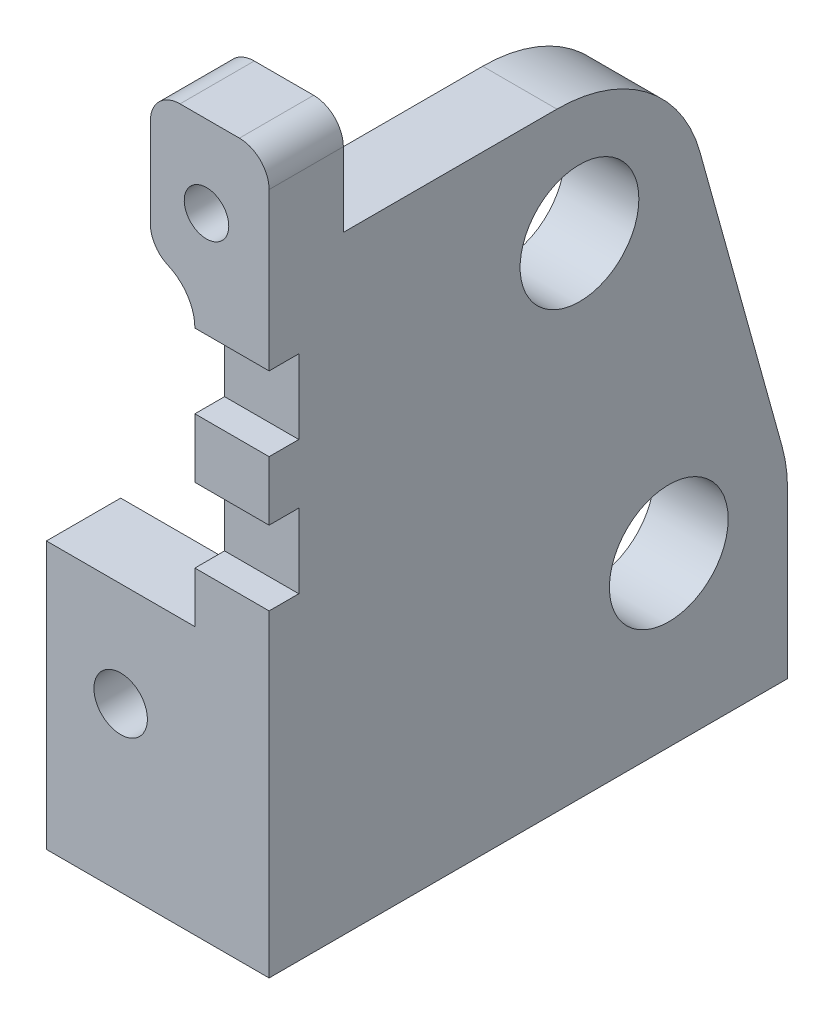
SolidWorks part; units mm, degrees
ref_plane "前视基准面" through (0, 0, 0) normal (0, 0, 1) x (1, 0, 0)
ref_plane "上视基准面" through (0, 0, 0) normal (0, 1, 0) x (1, 0, 0)
ref_plane "右视基准面" through (0, 0, 0) normal (1, 0, 0) x (0, 0, -1)
sketch "草图1" plane through (0, 0, 0) normal (1, 0, 0) x (0, 0, -1)
  line L1 (-20.9094, -33) -> (14.0173, -33)
  line L3 (-20.9094, 8) -> (-20.9094, -33)
  line L4 (-20.9094, 8) -> (6.082, 8)
  line L5 (6.082, 8) -> (14.0173, -20.5908)
  line L6 (14.0173, -20.5908) -> (14.0173, -33)
  line L7 (0, 0) -> (6.0173, -21.6804) construction
  circle A0 centre (0, 0) radius 4
  circle A1 centre (6.0173, -21.6804) radius 4
  point P13 (14.0173, -26.7954)
  dimension "D1" = 20.9094
  dimension "D5" = 8
  dimension "D7" = 8
  dimension "D2" = 33
  dimension "D3" = 22.5
  dimension "D4" = 21.6804
  dimension "D6" = 8
  dimension "D8" = 8
extrude "凸台-拉伸1" add sketch "草图1" along normal blind 5
sketch "草图2" plane through (0, 0, 0) normal (-1, 0, 0) x (0, 0, 1)
  line L0 (20.9094, -15) -> (20.9094, -33)
  line L1 (20.9094, 8) -> (20.9094, -33) construction
  line L3 (20.9094, -33) -> (7.9094, -33)
  line L4 (20.9094, -33) -> (-14.0173, -33) construction
  line L5 (7.9094, -33) -> (7.9094, -28)
  line L6 (7.9094, -28) -> (15.9094, -28)
  line L7 (15.9094, -28) -> (15.9094, -15)
  line L8 (15.9094, -15) -> (20.9094, -15)
  dimension "D1" = 5
  dimension "D2" = 5
  dimension "D3" = 13
  dimension "D4" = 8
extrude "凸台-拉伸2" add sketch "草图2" along normal blind 10
fillet "圆角1" radius 10 2 edges at (2.5, -20.5908, -14.0173) (2.5, 8, -6.082)
sketch "草图7" plane through (0, 8, 0) normal (0, 1, 0) x (1, 0, 0)
  line L1 (5, -20.9094) -> (-3, -20.9094)
  line L2 (5, -20.9094) -> (5, -15.9094)
  line L3 (5, -15.9094) -> (-3, -15.9094)
  line L4 (-3, -20.9094) -> (-3, -15.9094)
  dimension "D1" = 5
  dimension "D2" = 8
extrude "凸台-拉伸3" add sketch "草图7" along normal blind 7 and the other way blind 3
hole_wizard "打孔尺寸(%根据十字)槽半沉头木螺钉的类型1" positions "草图3" profile "草图4" countersink size "M3" standard "GB" end condition through all
sketch "草图3" plane through (0, 0, 15.9094) normal (0, 0, -1) x (-1, 0, 0)
  line L0 (10, -15) -> (10, -28) construction
  line L1 (10, -28) -> (0, -28) construction
  point P0 (5, -22)
  point P11 (0, 0)
  point P12 (0, 0)
  point P13 (0, 0)
  dimension "D1" = 5
  dimension "D2" = 6
sketch "草图4" plane through (-5, -22, 15.9094) normal (1, 0, 0) x (0, 1, 0)
  line L0 (0, 0) -> (0, 5)
  line L1 (0, 5) -> (1.8, 5)
  line L2 (1.8, 5) -> (1.8, 1.5)
  line L3 (1.8, 1.5) -> (3.3, 0)
  line L5 (3.3, 0) -> (0, 0)
  line L6 (-1.8, 1.5) -> (-3.3, 0) construction
  line L11 (0, -6.35) -> (0, 107.95) construction
  dimension "通孔孔直径" = 3.6
  dimension "通孔孔深度" = 5
  dimension "近端锥形沉头孔直径" = 6.6
  dimension "近端锥形沉头孔角度" = 90
hole_wizard "打孔尺寸(%根据十字)槽半沉头木螺钉的类型2" positions "草图5" profile "草图6" countersink size "M3" standard "GB" end condition through all
sketch "草图5" plane through (0, -28, 0) normal (0, 1, 0) x (1, 0, 0)
  line L0 (-10, -7.9094) -> (0, -7.9094) construction
  line L2 (0, -1.5205) -> (0, -15.9094) construction
  point P0 (-5, -11.9094)
  dimension "D1" = 4
  dimension "D2" = 5
sketch "草图6" plane through (-5, -28, 11.9094) normal (1, 0, 0) x (0, 0, 1)
  line L0 (0, 0) -> (0, 5)
  line L1 (0, 5) -> (1.8, 5)
  line L2 (1.8, 5) -> (1.8, 1.5)
  line L3 (1.8, 1.5) -> (3.3, 0)
  line L5 (3.3, 0) -> (0, 0)
  line L6 (-1.8, 1.5) -> (-3.3, 0) construction
  line L11 (0, -6.35) -> (0, 107.95) construction
  dimension "通孔孔直径" = 3.6
  dimension "通孔孔深度" = 5
  dimension "近端锥形沉头孔直径" = 6.6
  dimension "近端锥形沉头孔角度" = 90
fillet "圆角2" radius 2 3 edges at (-3, 5, 18.4094) (-3, 15, 18.4094) (5, 15, 18.4094)
fillet "圆角3" radius 3 1 edges at (0, 5, 18.4094)
hole_wizard "大小mm Transitional 暗销孔1" positions "草图8" profile "草图9" hole size "Ø3.0" standard "GB" end condition through all
sketch "草图8" plane through (0, 0, 15.9094) normal (0, 0, -1) x (-1, 0, 0)
  line L0 (-16.2809, 0) -> (3.92, 0) construction
  point P0 (-0.7825, 9.5089)
  point P8 (0, 0)
  point P13 (-7.9564, 0)
  dimension "D1" = 0.7825
  dimension "D2" = 9.5089
sketch "草图9" plane through (0.7825, 9.5089, 15.9094) normal (1, 0, 0) x (0, 1, 0)
  line L0 (0, 0) -> (0, 5)
  line L1 (0, 5) -> (1.5, 5)
  line L2 (1.5, 5) -> (1.5, 0)
  line L5 (1.5, 0) -> (0, 0)
  line L11 (0, -6.35) -> (0, 107.95) construction
  dimension "通孔孔直径" = 3
  dimension "通孔孔深度" = 5
sketch "草图10" plane through (0, 0, 0) normal (-1, 0, 0) x (0, 0, 1)
  line L1 (20.9094, 2.4174) -> (18.9094, 2.4174)
  line L2 (20.9094, 2.4174) -> (20.9094, -2.5826)
  line L3 (20.9094, -2.5826) -> (18.9094, -2.5826)
  line L4 (18.9094, 2.4174) -> (18.9094, -2.5826)
  line L5 (20.9094, -6.5826) -> (18.9094, -6.5826)
  line L6 (20.9094, -6.5826) -> (20.9094, -11.5826)
  line L7 (20.9094, -11.5826) -> (18.9094, -11.5826)
  line L8 (18.9094, -6.5826) -> (18.9094, -11.5826)
  line L9 (20.9094, 2.4174) -> (20.9094, -15) construction
  point P9 (0, 0)
  point P11 (0, 0)
  point P12 (0, 0)
  point P13 (0, 0)
  dimension "D1" = 2
  dimension "D2" = 5
  dimension "D3" = 5
  dimension "D4" = 4
extrude "切除-拉伸1" cut sketch "草图10" against normal through all
